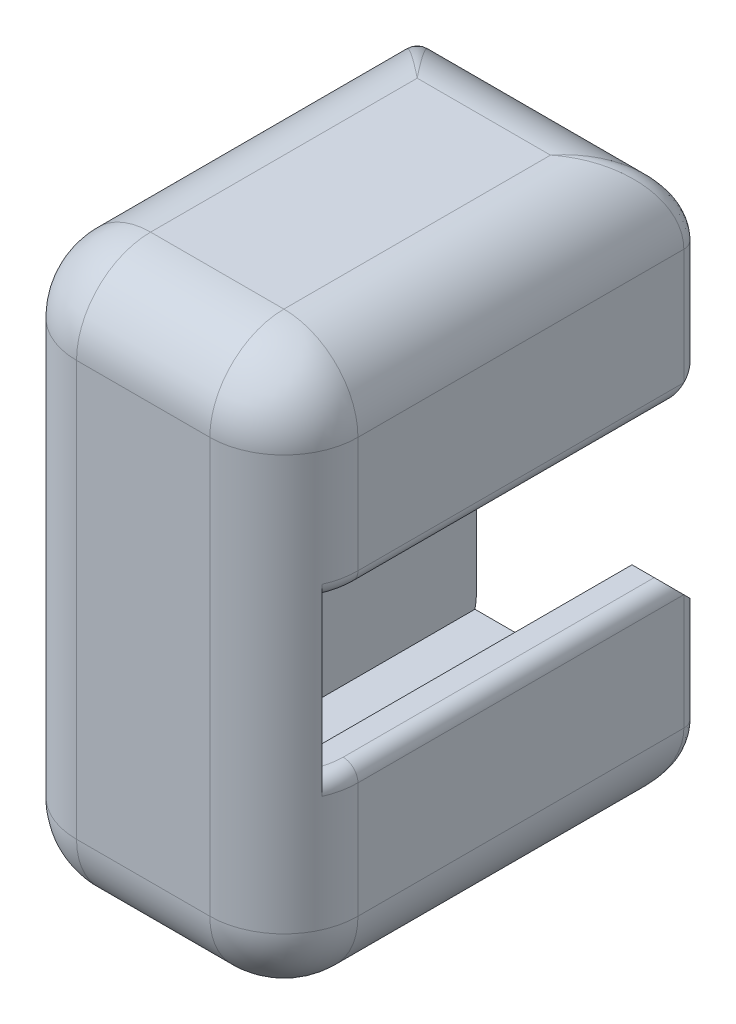
SolidWorks part; units mm, degrees
ref_plane "前视基准面" through (0, 0, 0) normal (0, 0, 1) x (1, 0, 0)
ref_plane "上视基准面" through (0, 0, 0) normal (0, 1, 0) x (1, 0, 0)
ref_plane "右视基准面" through (0, 0, 0) normal (1, 0, 0) x (0, 0, -1)
other "Configuration Table"
sketch "草图1" plane through (0, 0, 0) normal (0, 0, 1) x (1, 0, 0)
  line L1 (-9.5, 19) -> (9.5, 19)
  line L2 (-9.5, 19) -> (-9.5, -19)
  line L3 (-9.5, -19) -> (9.5, -19)
  line L4 (9.5, 19) -> (9.5, -19)
  line L5 (-9.5, 19) -> (9.5, -19) construction
  line L6 (-9.5, -19) -> (9.5, 19) construction
  point P0 (0, 0)
  dimension "D1" = 38
  dimension "D2" = 19
extrude "凸台-拉伸1" add sketch "草图1" along normal blind 3
sketch "草图2" plane through (0, 0, 0) normal (0, 0, -1) x (-1, 0, 0)
  line L0 (-9.5, 19) -> (9.5, 19)
  line L1 (9.5, -19) -> (9.5, 19)
  line L2 (9.5, 19) -> (9.5, -19) construction
  line L3 (9.5, -19) -> (-9.5, -19)
  line L4 (-9.5, -19) -> (-9.5, -15)
  line L5 (-9.5, -19) -> (-9.5, 19) construction
  line L6 (-9.5, -15) -> (5.5, -15)
  line L7 (5.5, -15) -> (5.5, 15)
  line L8 (5.5, 15) -> (-9.5, 15)
  line L9 (-9.5, 15) -> (-9.5, 19)
  point P5 (5.5, 0)
  dimension "D1" = 30
  dimension "D2" = 4
extrude "凸台-拉伸2" add sketch "草图2" along normal blind 25
sketch "草图5" plane through (9.5, 0, 0) normal (1, 0, 0) x (0, 0, -1)
  line L0 (25, 15) -> (25, -15) construction
  line L1 (0, 15) -> (25, 15)
  line L2 (0, 15) -> (0, 5.2)
  line L3 (0, 5.2) -> (25, 5.2)
  line L4 (25, 15) -> (25, 5.2)
  line L5 (0, 0) -> (35.361, 0) construction
  line L6 (0, -15) -> (0, 15) construction
  line L7 (25, -15) -> (25, -5.2)
  line L8 (0, -5.2) -> (25, -5.2)
  line L9 (0, -15) -> (0, -5.2)
  line L10 (0, -15) -> (25, -15)
  dimension "D1" = 10.4
extrude "凸台-拉伸3" add sketch "草图5" against normal blind 2.5
chamfer "倒角1" distance 2 angle 45 2 edges at (8.25, -5.2, -25) (8.25, 5.2, -25)
fillet "圆角2" radius 5 10 edges at (9.5, -19, -11) (0, -19, -25) (-9.5, -19, -11) (-9.5, 19, -11) (0, 19, -25) (9.5, 19, -11) (0, -19, 3) (-9.5, 0, 3) (0, 19, 3) (9.5, 0, 3)
fillet "圆角3" radius 1 3 edges at (-8.0355, -17.5355, -23.5355) (-8.0355, 17.5355, -23.5355) (-9.5, 0, -25)
fillet "圆角4" radius 1 8 edges at (9.3945, 5.2, -0.9785) (9.3945, -5.2, -0.9785) (8.0355, -17.5355, -23.5355) (8.0355, 17.5355, -23.5355) (9.5, 5.2, -12.5) (9.5, -5.2, -12.5) (9.5, -10.6, -25) (9.5, 10.6, -25)
